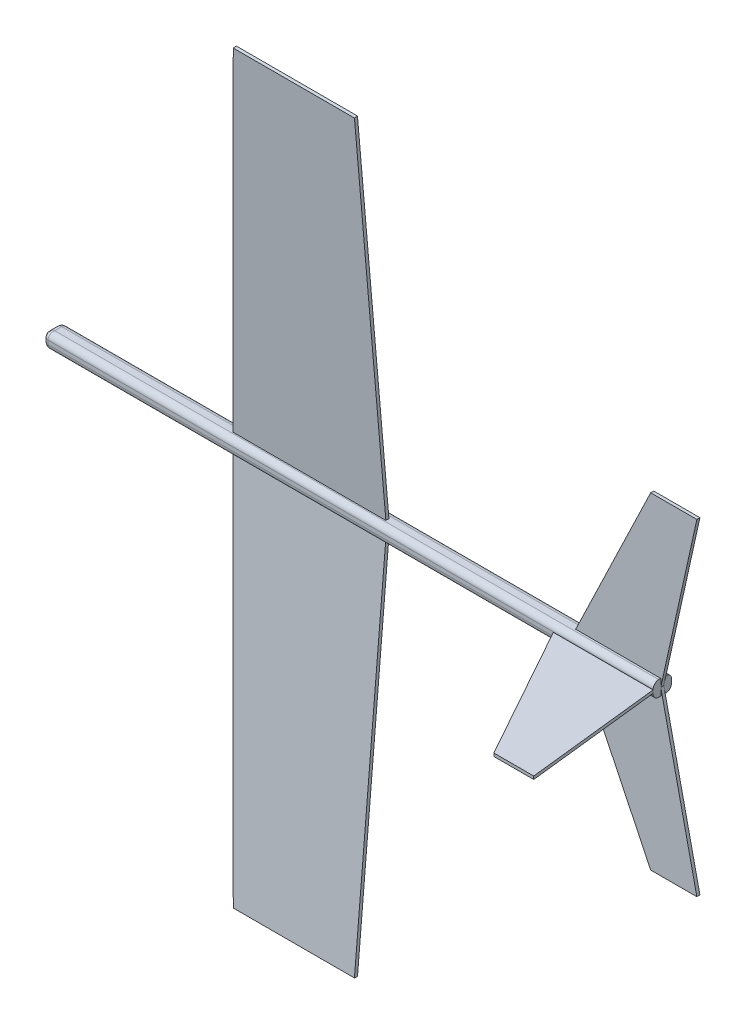
SolidWorks part; units mm, degrees
ref_plane "Front Plane" through (0, 0, 0) normal (0, 0, 1) x (1, 0, 0)
ref_plane "Top Plane" through (0, 0, 0) normal (0, 1, 0) x (1, 0, 0)
ref_plane "Right Plane" through (0, 0, 0) normal (1, 0, 0) x (0, 0, -1)
sketch "Sketch1" plane through (0, 0, 0) normal (0, 0, 1) x (1, 0, 0)
  line L0 (-159, 0) -> (159, 0) construction
  line L1 (159, 4) -> (-159, 4)
  line L2 (159, 4) -> (159, -4)
  line L3 (159, -4) -> (-159, -4)
  line L4 (-159, 4) -> (-159, -4)
  line L5 (159, 4) -> (-159, -4) construction
  line L6 (159, -4) -> (-159, 4) construction
  point P0 (0, 0)
  dimension "D1" = 8
  dimension "D2" = 318
extrude "Boss-Extrude1" add sketch "Sketch1" along normal mid plane 9.6
ref_plane "Plane3" through (0, 0, 0) normal (0, -0.0872, 0.9962) x (1, 0, 0)
sketch "Sketch3" plane through (0, 0, 0) normal (0, -0.0872, 0.9962) x (1, 0, 0)
  line L0 (-64, 0) -> (-46.9397, 195)
  line L1 (-46.9397, 195) -> (16.2603, 195)
  line L2 (16.2603, 195) -> (16, 0)
  line L3 (16, 0) -> (-64, 0)
  line L4 (-159, 4.4031) -> (-159, 3.5664) construction
  dimension "D1" = 95
  dimension "D2" = 80
  dimension "D3" = 63.2
  dimension "D4" = 195
  dimension "D5" = 85
extrude "Boss-Extrude2" add sketch "Sketch3" along normal mid plane 1.5875 contours L2 L3 L0 L1
mirror "Mirror1" about plane through (0, 0, 0) normal (0, 1, 0) of "Boss-Extrude2"
sketch "Sketch6" plane through (0, 0, 0) normal (0, 1, 0) x (1, 0, 0)
  line L0 (159, -4.8) -> (166.766, -74.8)
  line L1 (166.766, -74.8) -> (145.966, -74.8)
  line L2 (145.966, -74.8) -> (107, -4.8)
  line L3 (-159, -4.8) -> (159, -4.8) construction
  line L4 (107, -4.8) -> (159, -4.8)
  line L5 (151.166, -74.8) -> (120, -4.8) construction
  line L6 (159, -4.8) -> (-159, -4.8) construction
  dimension "D1" = 20.8
  dimension "D2" = 52
  dimension "D4" = 66
  dimension "D3" = 13
  dimension "D5" = 5.2
  dimension "D6" = 70
extrude "Boss-Extrude3" add sketch "Sketch6" along normal mid plane 1.5875 contours L0 L1 L2 L4
sketch "Sketch8" plane through (0, 0, 0) normal (0, 0, 1) x (1, 0, 0)
  line L0 (159, 0) -> (177.8349, 85.2)
  line L1 (5.28, 0) -> (-5.28, 0) construction
  line L2 (177.8349, 85.2) -> (153.7589, 85.2)
  line L3 (153.7589, 85.2) -> (112.7, 0)
  line L4 (112.7, 0) -> (159, 0)
  line L5 (159, -4) -> (159, -0.7937) construction
  dimension "D1" = 24.076
  dimension "D2" = 46.3
  dimension "D4" = 64.27
  dimension "D3" = 85.2
extrude "Boss-Extrude4" add sketch "Sketch8" along normal mid plane 1.5875 contours L0 L2 L3 L4
mirror "Mirror2" about plane through (0, 0, 0) normal (0, 1, 0) of "Boss-Extrude4"
fillet "Fillet1" radius 2.5 2 edges at (-159, 0, -4.8) (-159, 0, 4.8)
fillet "Fillet2" radius 3 10 edges at (1.25, 4, -4.8) (-158.2678, 4, -4.0678) (-159, 4, 0) (-158.2678, 4, 4.0678) (1.25, -4, -4.8) (-158.2678, -4, -4.0678) (-159, -4, 0) (-158.2678, -4, 4.0678) (1.25, 4, 4.8) (1.25, -4, 4.8)
sketch "Sketch9" plane through (156.5407, 0, -17.3671) normal (0.9939, 0, -0.1103) x (-0.1103, 0, -0.9939)
  line L0 (-69.5393, -0.7937) -> (-69.5393, 0.7937)
  line L1 (-22.3031, -0.7937) -> (-92.7326, -0.7937) construction
  line L2 (-22.3031, 0.7938) -> (-92.7326, 0.7937) construction
  line L3 (-69.5393, 0.7937) -> (-66.4139, 0.7938)
  line L4 (-66.4139, 0.7938) -> (-66.4139, -0.7937)
  line L5 (-66.4139, -0.7937) -> (-69.5393, -0.7937)
  line L6 (-57.5178, 5.8406) -> (-57.5178, -7.9609) construction
  line L7 (-45.4964, -0.7937) -> (-45.4964, 0.7937)
  line L8 (-48.6217, 0.7938) -> (-48.6217, -0.7937)
  line L9 (-48.6217, -0.7937) -> (-45.4964, -0.7937)
  line L10 (-45.4964, 0.7937) -> (-48.6217, 0.7938)
equation "\"Wing Root chord\"= 8cm"
equation "\"Taper Ratio\"= 0.79"
equation "\"Wing Tip chord\"= \"Wing Root chord\" * \"Taper Ratio\""
equation "\"D2@Sketch3\"=\"Wing Root chord\""
equation "\"D3@Sketch3\"=\"Wing Tip chord\""
equation "\"Vertical Wing Root chord\"= 5.2"
equation "\"Vertical Wing Taper Ratio\"= 0.4"
equation "\"Vertical Wing Tip chord\"= \"Vertical Wing Root chord\" * \"Vertical Wing Taper Ratio\""
equation "\"D1@Sketch6\"=\"Vertical Wing Tip chord\""
equation "\"D2@Sketch6\"=\"Vertical Wing Root chord\""
equation "\"Stabilizer Root Chord\"= 4.63cm"
equation "\"Stabilizer Taper Ratio\"= 0.52'S"
equation "\"Stabilizer Tip chord\"= \"Stabilizer Root Chord\" * \"Stabilizer Taper Ratio\""
equation "\"D1@Sketch8\"=\"Stabilizer Tip chord\""
equation "\"D2@Sketch8\"=\"Stabilizer Root Chord\""
